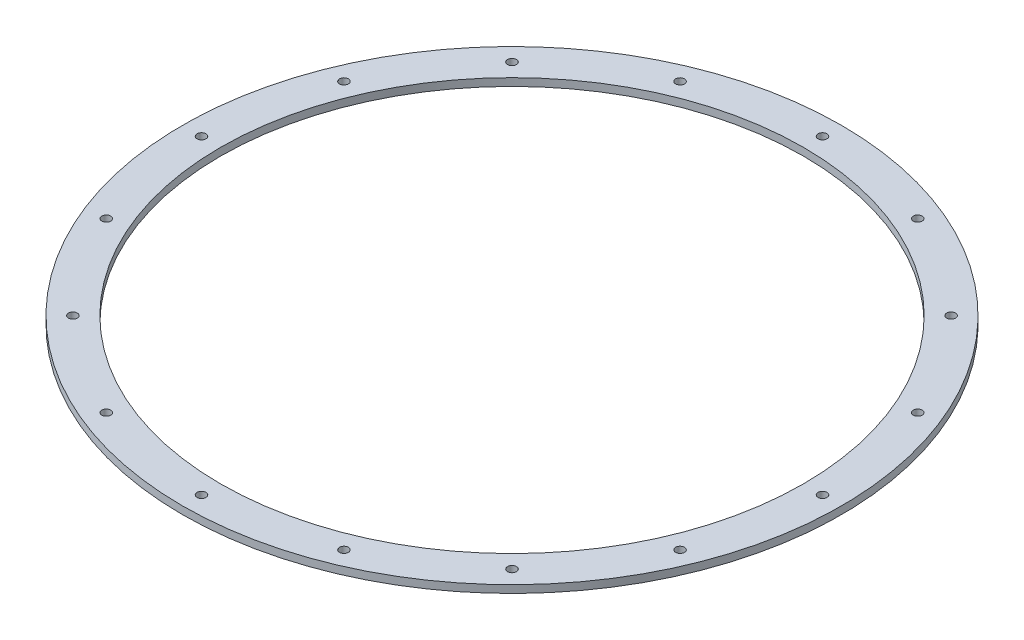
SolidWorks part; units mm, degrees
material "AISI 304"
ref_plane "Piano frontale" through (0, 0, 0) normal (0, 0, 1) x (1, 0, 0)
ref_plane "Piano superiore" through (0, 0, 0) normal (0, 1, 0) x (1, 0, 0)
ref_plane "Piano destro" through (0, 0, 0) normal (1, 0, 0) x (0, 0, -1)
sketch "Schizzo1" plane through (0, 0, 0) normal (0, 1, 0) x (1, 0, 0)
  line L1 (0, -300) -> (0, 300) construction
  line L66 (332.921, 0) -> (-332.921, 0) construction
  circle A0 centre (0, 0) radius 229.5
  circle A92 centre (0, 0) radius 259.5
  circle A93 centre (0, 0) radius 244.5 construction
  circle A94 centre (0, 244.5) radius 3.5
  circle A95 centre (93.5661, 225.8885) radius 3.5
  circle A96 centre (172.8876, 172.8876) radius 3.5
  circle A97 centre (225.8885, 93.5661) radius 3.5
  circle A98 centre (244.5, 0) radius 3.5
  circle A99 centre (225.8885, -93.5661) radius 3.5
  circle A100 centre (172.8876, -172.8876) radius 3.5
  circle A101 centre (93.5661, -225.8885) radius 3.5
  circle A102 centre (0, -244.5) radius 3.5
  circle A103 centre (-93.5661, -225.8885) radius 3.5
  circle A104 centre (-172.8876, -172.8876) radius 3.5
  circle A105 centre (-225.8885, -93.5661) radius 3.5
  circle A106 centre (-244.5, 0) radius 3.5
  circle A107 centre (-225.8885, 93.5661) radius 3.5
  circle A108 centre (-172.8876, 172.8876) radius 3.5
  circle A109 centre (-93.5661, 225.8885) radius 3.5
  point P3 (327.921, 50)
  point P5 (367.2297, 50)
  point P6 (-327.921, 50)
  point P7 (0, 0)
  point P8 (-340, -300)
  point P9 (-340, 300)
  point P11 (-385, -300)
  point P27 (0, 0)
  point P28 (-367.2297, 50)
  point P29 (367.2297, -50)
  point P30 (-367.2297, -50)
  point P33 (-340, -300)
  point P34 (0, 0)
  point P36 (0, 0)
  point P37 (-385, 300)
  point P38 (-340, 300)
  point P40 (0, 0)
  point P41 (327.921, -50)
  point P43 (300, 50)
  point P44 (-300, 50)
  point P45 (-330, -300)
  point P47 (-330, 300)
  point P48 (0, 0)
  point P52 (0, 0)
  point P55 (0, 0)
  point P56 (-385, -126.1125)
  point P57 (0, 0)
  point P58 (-327.921, -50)
  point P62 (-385, 126.1125)
  point P63 (-335, -300)
  point P66 (-335, 300)
  point P67 (0, 0)
  point P69 (0, 0)
  point P71 (0, 0)
  point P72 (300, -50)
  point P75 (-300, -50)
  point P81 (0, 0)
  point P85 (0, 0)
  point P87 (0, 0)
  point P88 (-280, -300)
  point P89 (-280, 300)
  point P92 (0, 0)
  point P95 (0, 0)
  point P98 (0, 0)
  point P105 (0, 0)
  dimension "D1" = 30
  dimension "D2" = 15
  dimension "D3" = 16
extrude "Estrusione-Estrusione1" add sketch "Schizzo1" along normal mid plane 6
ref_axis "Assi1" through (0, 3, 0) along (0, -1, 0)
sketch "Schizzo2" plane through (0, 3, 0) normal (0, 1, 0) x (1, 0, 0)
  line L0 (0, -59.8354) -> (0, 59.8354) construction
  line L1 (64.2339, 0) -> (-64.2339, 0) construction
  point P5 (0, 0)
  point P9 (0, 0)
sketch "Schizzo3" plane through (0, -3, 0) normal (0, -1, 0) x (1, 0, 0)
  line L0 (0, -125) -> (0, 125) construction
  line L1 (125, 0) -> (-125, 0) construction
  point P4 (0, 0)
  point P8 (0, 0)
